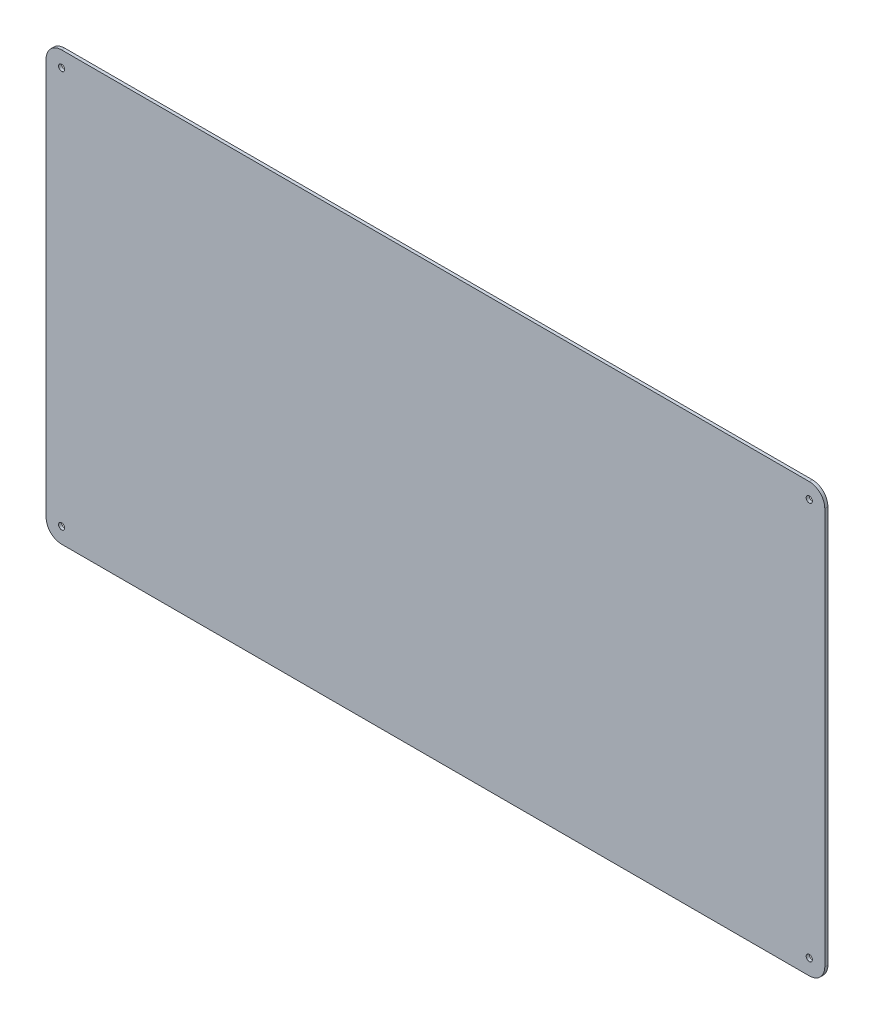
SolidWorks part; units mm, degrees
material "Galvanized Steel"
ref_plane "Front" through (0, 0, 0) normal (0, 0, 1) x (1, 0, 0)
ref_plane "Top" through (0, 0, 0) normal (0, 1, 0) x (1, 0, 0)
ref_plane "Right" through (0, 0, 0) normal (1, 0, 0) x (0, 0, -1)
sketch "Sketch1" plane through (0, 0, 0) normal (0, 0, 1) x (1, 0, 0)
  line L1 (5, 0) -> (246, 0)
  line L2 (0, 5) -> (0, 133)
  line L3 (5, 138) -> (246, 138)
  line L4 (251, 5) -> (251, 133)
  circle A1 centre (5, 133) radius 1
  circle A2 centre (5, 5) radius 1
  circle A5 centre (246, 133) radius 1
  circle A6 centre (246, 5) radius 1
  arc A7 (246, 138) -> (251, 133) centre (246, 133) cw
  arc A8 (251, 5) -> (246, 0) centre (246, 5) cw
  arc A9 (0, 5) -> (5, 0) centre (5, 5) ccw
  arc A10 (0, 133) -> (5, 138) centre (5, 133) cw
  point P15 (251, 138)
  point P18 (251, 0)
  point P21 (0, 0)
  point P24 (0, 138)
  dimension "D3" = 5
  dimension "D4" = 241
  dimension "D1" = 251
  dimension "D2" = 138
  dimension "D5" = 128
base flange "Base-Flange1" sketch "Sketch1" thickness 1 reverse thickness direction no parameters "D1"=10
sketch "Bend-Lines1" [suppressed] plane through (0, 0, 0) normal (0, 1, 0) x (1, 0, 0)
sketch "Bounding-Box1" [suppressed] plane through (0, 0, 0) normal (0, 1, 0) x (1, 0, 0)
sheet metal parameters "Sheet-Metal1" thickness 1 parameters "D1"=10
flat pattern "Flat-Pattern1" [suppressed]
sketch "Bend-Lines2" plane through (0, 0, 0) normal (0, 1, 0) x (1, 0, 0)
sketch3d "Bounding-Box2" [suppressed]
  line L0 (-246, 5, 0) -> (5, 5, 0) construction
  line L1 (-246, -133, 0) -> (5, -133, 0) construction
  line L2 (-246, 5, 0) -> (-246, -133, 0) construction
  line L3 (5, 5, 0) -> (5, -133, 0) construction
